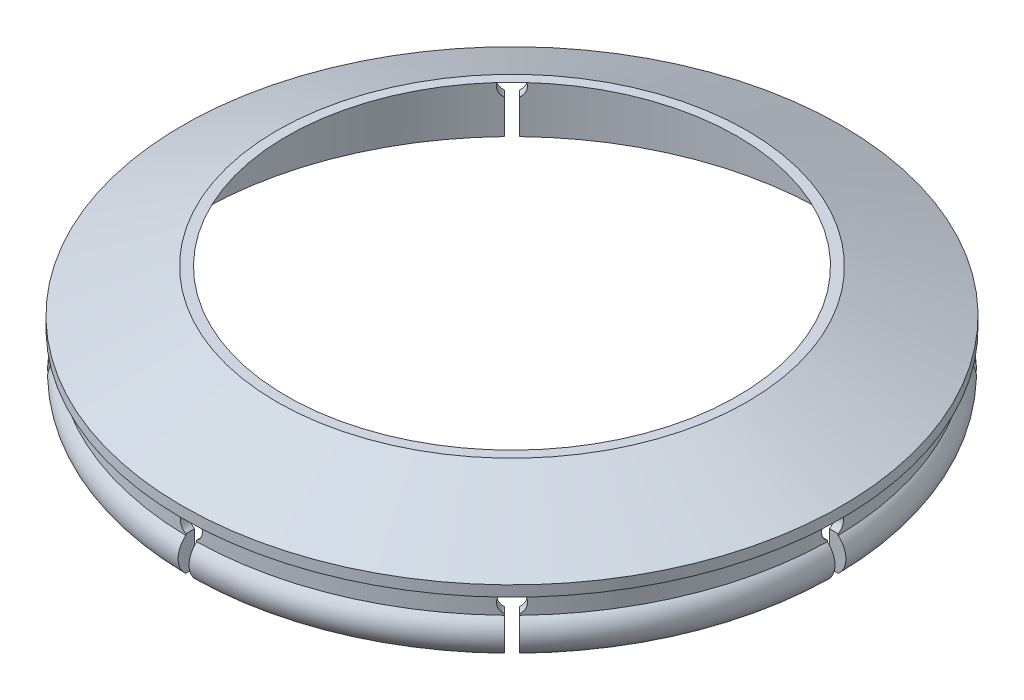
SolidWorks part; units mm, degrees
ref_plane "Front Plane" through (0, 0, 0) normal (0, 0, 1) x (1, 0, 0)
ref_plane "Top Plane" through (0, 0, 0) normal (0, 1, 0) x (1, 0, 0)
ref_plane "Right Plane" through (0, 0, 0) normal (1, 0, 0) x (0, 0, -1)
sketch "Sketch1" plane through (0, 0, 0) normal (0, 0, 1) x (1, 0, 0)
  line L0 (0, 0) -> (0, 42) construction
  line L1 (0, 0) -> (-28.5, 0) construction
  line L2 (-28.5, 0) -> (-28.5, 42) construction
  line L3 (-28.5, 42) -> (0, 42) construction
  line L4 (-28.5, 0) -> (-28.5, 0.8) construction
  line L6 (-11, 20) -> (-11, 42) construction
  line L7 (-11, 42) -> (-10.2, 42) construction
  line L11 (-28.5, 0) -> (-23.0662, 0) construction
  line L12 (-28.5, 0.8) -> (-23.5, 0.8) construction
  line L13 (-23.5, 0.8) -> (-11, 20) construction
  line L14 (-10.2, 19.7625) -> (-23.0662, 0) construction
  line L15 (0, 0) -> (0, -1) construction
  line L16 (0, -1) -> (-28.5, -1) construction
  line L17 (-10.2, 19.7625) -> (-10.2, 42) construction
  line L18 (-28.5, -1) -> (-28.5, 0) construction
  line L20 (-10.2, -21.7625) -> (-23.0662, -2) construction
  line L21 (-10.2, -21.7625) -> (-10.2, -44) construction
  line L22 (-11, -44) -> (-10.2, -44) construction
  line L23 (-11, -22) -> (-11, -44) construction
  line L24 (-23.5, -2.8) -> (-11, -22) construction
  line L25 (-28.5, -2.8) -> (-23.5, -2.8) construction
  line L26 (-28.5, -5.6) -> (-28.5, -2.8) construction
  line L27 (-27.5, 0.8) -> (-27.5, 1.8) construction
  line L28 (-27.5, 1.8) -> (-20.8958, 4.8) construction
  line L29 (-20.8958, 4.8) -> (-23.5, 0.8) construction
  line L30 (-23.5, 0.8) -> (-27.5, 0.8) construction
  line L31 (-20.8958, -6.8) -> (-23.5, -2.8) construction
  line L32 (-27.5, -3.8) -> (-20.8958, -6.8) construction
  line L33 (-27.5, -2.8) -> (-27.5, -3.8) construction
  line L34 (-23.5, -2.8) -> (-27.5, -2.8) construction
  line L35 (-20.8958, 4.8) -> (-27.5, 1.8)
  line L36 (-27.5, 1.8) -> (-27.5, 0.8)
  line L37 (-27.5, 0.8) -> (-28.5, 0.8)
  line L38 (-28.5, 0.8) -> (-28.5, -5.6)
  line L39 (-28.5, -5.6) -> (-29.3, -5.6)
  line L42 (-19.2713, 7.2953) -> (-20.8958, 4.8)
  line L43 (-19.2713, 7.2953) -> (-30.1, 2.3763)
  line L46 (-30.1, 1.4) -> (-29.3, 1.4)
  line L47 (-29.3, 1.4) -> (-29.3, -0.6)
  line L48 (-29.3, -3.6) -> (-29.3, -5.6)
  line L49 (-30.1, 2.3763) -> (-30.1, 1.4)
  arc A0 (-29.3, -3.6) -> (-29.3, -0.6) centre (-28.0429, -2.1) cw
  point P37 (-30, -2.1)
  dimension "D10" = 0.8
  dimension "D11" = 1
  dimension "D14" = 56.934
  dimension "D13" = 0.8
  dimension "D2" = 28.5
  dimension "D3" = 0.8
  dimension "D4" = 42
  dimension "D5" = 22
  dimension "D6" = 11
  dimension "D7" = 1
  dimension "D8" = 1
  dimension "D9" = 5
  dimension "D12" = 4
  dimension "D15" = 3
  dimension "D16" = 1.6
  dimension "D17" = 2
  dimension "D18" = 0.7
  dimension ".7" = 2
  dimension "D21" = 6.4
  dimension "D22" = 0.8
sketch "Sketch2" plane through (0, 0, 0) normal (0, 0, 1) x (1, 0, 0)
  line L0 (-27.5, 1.8) -> (-20.8958, 4.8) construction
  line L1 (-27.5, 0.8) -> (-27.5, 1.8) construction
  line L2 (-28.5, 0.8) -> (-23.5, 0.8) construction
  line L3 (-10.2, 19.7625) -> (-23.0662, 0) construction
  line L4 (-23.5, 0.8) -> (-11, 20) construction
  line L5 (-10.2, 19.7625) -> (-10.2, 42) construction
  line L6 (-11, 20) -> (-11, 42) construction
  line L7 (-27.5, 1.8) -> (-20.8958, 4.8)
  line L8 (-27.5, 0.8) -> (-27.5, 1.8)
  line L9 (-28.5, 0.8) -> (-27.5, 0.8)
  line L10 (-10.2, 19.7625) -> (-23.0662, 0)
  line L11 (-20.8958, 4.8) -> (-11, 20)
  line L12 (-10.2, 19.7625) -> (-10.2, 42)
  line L13 (-11, 20) -> (-11, 42)
  line L14 (-28.5, 0.8) -> (-28.5, 0)
  line L15 (-28.5, 0) -> (-23.0662, 0)
  line L16 (-11, 42) -> (-10.2, 42)
sketch "Sketch3" plane through (0, 0, 0) normal (0, 0, 1) x (1, 0, 0)
  line L0 (-27.5, -2.8) -> (-27.5, -3.8)
  line L1 (-27.5, -3.8) -> (-20.8958, -6.8)
  line L2 (-20.8958, -6.8) -> (-19.2713, -9.2953)
  line L3 (-23.5, -2.8) -> (-11, -22) construction
  line L4 (-19.2713, -9.2953) -> (-31.7036, -3.6478)
  line L5 (-31.7036, -3.6478) -> (-31.7036, 1.4)
  line L6 (-31.7036, 1.4) -> (-29.3, 1.4)
  line L7 (-29.3, 1.4) -> (-29.3, -0.6)
  line L9 (-19.2713, 7.2953) -> (-20.8958, 4.8) construction
  line L10 (-29.3, -3.6) -> (-29.3, -2.8)
  line L11 (-29.3, -2.8) -> (-27.5, -2.8)
  arc A0 (-29.3, -0.6) -> (-29.3, -3.6) centre (-28.0429, -2.1) ccw construction
  arc A1 (-29.3, -0.6) -> (-29.3, -3.6) centre (-28.0429, -2.1) ccw
revolve "Revolve1" add sketch "Sketch1" angle 360 about L0
ref_plane "Plane1" through (0, 7.2953, 0) normal (0, 1, 0) x (1, 0, 0)
sketch "Sketch4" plane through (0, 7.2953, 0) normal (0, 1, 0) x (1, 0, 0)
  circle A0 centre (0, 0) radius 21
  dimension "D1" = 42
extrude "Cut-Extrude1" cut sketch "Sketch4" against normal blind 1 draft 39 draft outward yes
sketch "Sketch5" plane through (0, 0, 0) normal (0, 0, 1) x (1, 0, 0)
  line L0 (-29.3, -5.6) -> (29.3, -5.6) construction
  line L1 (-29.3, -5.6) -> (-28.5, -5.6)
  line L2 (-29.3, -5.6) -> (-29.3, -5)
  line L3 (-29.3, -5) -> (-28.5, -5)
  line L4 (-28.5, -5.6) -> (-28.5, -5)
  line L5 (-28.5, -5.6) -> (28.5, -5.6) construction
  line L6 (-28.5, -5.6) -> (28.5, -5.6) construction
  line L7 (-29.3, -5.6) -> (-29.3, -3.6)
  line L8 (29.3, -3.6) -> (29.3, -5.6)
  line L9 (29.3, -3.6) -> (29.3, -5.6)
  line L10 (-29.3, -5.6) -> (-29.3, -3.6) construction
  line L11 (0, 0) -> (0, 19.8395) construction
  dimension "D1" = 0.6
revolve "Cut-Revolve2" cut sketch "Sketch5" angle 360 about L11
sketch "Sketch6" plane through (0, 0, 0) normal (0, 0, 1) x (1, 0, 0)
  line L0 (-0.5, -5) -> (0.5, -5)
  line L1 (0.5, -5) -> (0.5, -0.466)
  line L3 (-0.5, -0.466) -> (-0.5, -5)
  line L4 (0, -5) -> (0, 0.4) construction
  line L5 (-29.3, -5) -> (29.3, -5) construction
  line L6 (-29.3, 1.4) -> (29.3, 1.4) construction
  line L7 (0, 0) -> (0, 4.3377) construction
  arc A0 (0.5, -0.466) -> (-0.5, -0.466) centre (0, 0.4) ccw
  dimension "D1" = 1
  dimension "D2" = 1
extrude "Cut-Extrude2" cut sketch "Sketch6" along normal through all
pattern_circular "CirPattern1" count 8 over 360 about axis through (0, 0, 0) along (0, -1, 0) of "Cut-Extrude2" reverse direction yes
sketch "Sketch7" plane through (0, 0, 0) normal (0, 0, 1) x (1, 0, 0)
  line L0 (-28.4853, 0.8) -> (-27.5, 0.8)
  line L1 (-27.5, 0.8) -> (-27.5, 1.8)
  line L2 (-27.5, 1.8) -> (-28.4853, 0.8)
  line L3 (-20.8958, 4.8) -> (-27.5, 1.8)
  line L4 (27.5, 1.8) -> (20.8958, 4.8)
  line L5 (27.5, 1.8) -> (20.8958, 4.8) construction
  line L6 (-20.8958, 4.8) -> (-27.5, 1.8)
  line L7 (-27.5, 1.8) -> (-27.5, 1.4)
  line L8 (27.5, 1.4) -> (27.5, 1.8)
  line L9 (27.5, 1.4) -> (27.5, 1.8) construction
  line L10 (-27.5, 1.8) -> (-27.5, 0.8)
  line L12 (-20.0827, 0.8) -> (-20.7902, 0.8) construction
  line L13 (-27.5, 0.8) -> (-28.4853, 0.8)
  line L14 (-28.4853, 0.8) -> (-20.7902, 0.8) construction
  line L15 (0, 0) -> (0, 13.334) construction
  point P4 (-28.1035, 0.7833)
  point P7 (-27.5, 0.9038)
  point P11 (0, 0)
  point P16 (0, 0)
  point P19 (-28.4853, 0.3891)
revolve "Cut-Revolve4" cut sketch "Sketch7" angle 360 about L15 region at (-27.8284, 1.1333, 0)
sketch "Sketch9" plane through (0, -5, 0) normal (0, -1, 0) x (1, 0, 0)
  circle A0 centre (0, 0) radius 30
extrude "Cut-Extrude3" cut sketch "Sketch9" against normal up to vertex (1.4 mm away) up to point (-0.5, -3.6, 29.2957)
sketch "Sketch10" plane through (0, 0, 0) normal (0, 0, 1) x (1, 0, 0)
  line L0 (-28.4853, 0.8) -> (-28.4853, 2)
  line L1 (-28.4853, 2) -> (-24.234, 4.6319)
  line L2 (-24.234, 4.6319) -> (-20.5723, 6.2953)
  line L3 (19.9223, 6.2953) -> (-19.9223, 6.2953) construction
  line L4 (-19.9223, 6.2953) -> (-20.8958, 4.8)
  line L5 (20.8958, 4.8) -> (19.9223, 6.2953)
  line L6 (20.8958, 4.8) -> (19.9223, 6.2953) construction
  line L7 (-19.9223, 6.2953) -> (-20.8958, 4.8)
  line L8 (-19.9223, 6.2953) -> (-20.5723, 6.2953)
  line L9 (-20.8958, 4.8) -> (-27.5, 1.8)
  line L10 (27.5, 1.8) -> (20.8958, 4.8)
  line L11 (27.5, 1.8) -> (20.8958, 4.8) construction
  line L12 (-20.8958, 4.8) -> (-27.5, 1.8)
  line L13 (-27.8941, 1.4) -> (-27.5, 1.8)
  line L14 (27.5, 1.8) -> (27.8941, 1.4)
  line L15 (27.5, 1.8) -> (27.8941, 1.4) construction
  line L16 (-27.8941, 1.4) -> (-27.5, 1.8)
  line L19 (-29.3, 1.4) -> (-27.8941, 1.4)
  line L20 (-29.3, 1.4) -> (-27.8941, 1.4) construction
  line L21 (-28.4853, 0.8) -> (-27.8941, 1.4)
  line L22 (-30.1, 2.3763) -> (-21.4727, 6.2953)
  line L23 (21.4727, 6.2953) -> (30.1, 2.3763)
  line L24 (21.4727, 6.2953) -> (30.1, 2.3763) construction
  line L25 (-30.1, 2.3763) -> (-21.4727, 6.2953)
  line L26 (0, 0) -> (0, 18.0799) construction
  dimension "D1" = 0.65
  dimension "D2" = 0.3724
  dimension "D3" = 1.2
  dimension "D4" = 5
revolve "Cut-Revolve5" cut sketch "Sketch10" angle 360 about L26 region at (-28.2882, 1.2, 0) region at (-24.0469, 3.9781, 0)
